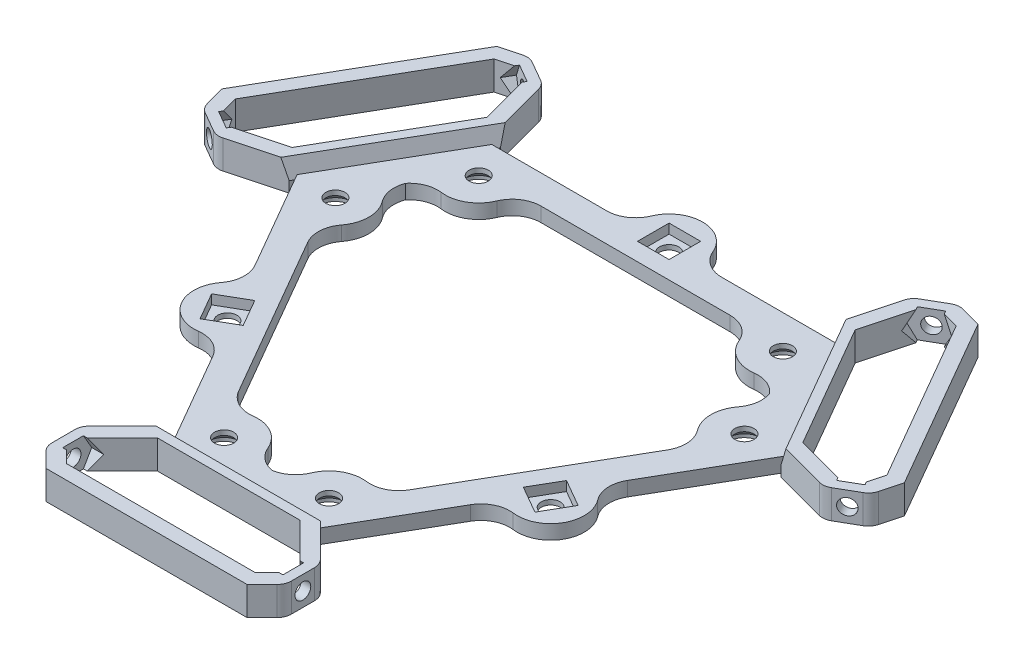
SolidWorks part; units mm, degrees
note: '?' marks a value the reader was unsure of.
ref_plane "Front Plane" through (0, 0, 0) normal (0, 0, 1) x (1, 0, 0)
ref_plane "Top Plane" through (0, 0, 0) normal (0, 1, 0) x (1, 0, 0)
ref_plane "Right Plane" through (0, 0, 0) normal (1, 0, 0) x (0, 0, -1)
sketch "Sketch1" plane through (0, 0, 0) normal (0, 1, 0) x (1, 0, 0)
  line L0 (-55.8013, 3.3494) -> (-30.8013, 46.6506) construction
  line L1 (50.8013, 12.0096) -> (35.8013, 37.9904)
  line L2 (35.8013, 37.9904) -> (-35.8013, 37.9904)
  line L3 (-35.8013, 37.9904) -> (-50.8013, 12.0096)
  line L4 (-50.8013, 12.0096) -> (-15, -50)
  line L5 (-15, -50) -> (15, -50)
  line L6 (15, -50) -> (50.8013, 12.0096)
  line L7 (55.8013, 3.3494) -> (30.8013, 46.6506) construction
  line L8 (-25, -50) -> (25, -50) construction
  line L9 (-43.8731, 12.0096) -> (-11.5359, -44) construction
  line L10 (-11.5359, -44) -> (11.5359, -44) construction
  line L11 (11.5359, -44) -> (43.8731, 12.0096) construction
  line L12 (43.8731, 12.0096) -> (32.3372, 31.9904) construction
  line L13 (32.3372, 31.9904) -> (-32.3372, 31.9904) construction
  line L14 (-32.3372, 31.9904) -> (-43.8731, 12.0096) construction
  line L15 (-43.8731, 12.0096) -> (-50.8013, 12.0096) construction
  line L16 (-32.3372, 31.9904) -> (-35.8013, 37.9904) construction
  line L17 (32.3372, 31.9904) -> (35.8013, 37.9904) construction
  line L18 (43.8731, 12.0096) -> (50.8013, 12.0096) construction
  line L19 (11.5359, -44) -> (15, -50) construction
  line L20 (-11.5359, -44) -> (-15, -50) construction
  line L21 (-40.1203, 18.5096) -> (-36.0899, 25.4904)
  line L22 (24.8316, 31.9904) -> (-24.8316, 31.9904)
  line L23 (-40.1203, 5.5096) -> (-15.2887, -37.5)
  line L24 (-4.0303, -44) -> (4.0303, -44)
  line L25 (40.1203, 5.5096) -> (15.2887, -37.5)
  line L26 (40.1203, 18.5096) -> (36.0899, 25.4904)
  circle A0 centre (0, 0) radius 37.9904 construction
  circle A1 centre (0, 0) radius 50 construction
  arc A2 (-40.1203, 5.5096) -> (-40.1203, 18.5096) centre (-42.7184, 12.0096) ccw
  arc A3 (-36.0899, 25.4904) -> (-24.8316, 31.9904) centre (-31.7598, 30.9904) ccw
  arc A4 (24.8316, 31.9904) -> (36.0899, 25.4904) centre (31.7598, 30.9904) ccw
  arc A5 (40.1203, 18.5096) -> (40.1203, 5.5096) centre (42.7184, 12.0096) ccw
  arc A6 (15.2887, -37.5) -> (4.0303, -44) centre (10.9585, -43) ccw
  arc A7 (-4.0303, -44) -> (-15.2887, -37.5) centre (-10.9585, -43) ccw
  circle A8 centre (-42.7184, 12.0096) radius 7 construction
  point P13 (-43.3013, 25)
  point P16 (43.3013, 25)
  point P19 (0, -50)
  point P53 (0, 0)
  dimension "D4" = 3
  dimension "D5" = 14
  dimension "D6" = 100
  dimension "D1" = 50
  dimension "D2" = 10
  dimension "D3" = 6
extrude "Boss-Extrude1" add sketch "Sketch1" along normal blind 3
sketch "Sketch2" plane through (0, 0, 0) normal (0, -1, 0) x (1, 0, 0)
  line L0 (25, 60.85) -> (25, 58.85)
  line L1 (25, 58.85) -> (16.15, 50)
  line L2 (16.15, 50) -> (-16.15, 50)
  line L3 (-15, 50) -> (15, 50) construction
  line L4 (0, 50) -> (0, 53) construction
  line L5 (-14.9074, 53) -> (14.9074, 53)
  line L6 (14.9074, 53) -> (22.7574, 60.85)
  line L7 (22.7574, 60.85) -> (25, 60.85) construction
  line L8 (18.8324, 56.925) -> (20.9537, 54.8037) construction
  line L9 (-4.8365, 62.5) -> (49995.1635, 62.5) construction
  line L10 (-18.8324, 56.925) -> (-20.9537, 54.8037) construction
  line L11 (-22.7574, 60.85) -> (-25, 60.85) construction
  line L12 (-14.9074, 53) -> (-22.7574, 60.85)
  line L13 (-25, 58.85) -> (-16.15, 50)
  line L14 (-25, 60.85) -> (-25, 58.85)
  line L15 (-25, 60.85) -> (-25, 64.15)
  line L16 (-22.7574, 64.15) -> (-25, 64.15) construction
  line L17 (-22.7574, 64.15) -> (-22.7574, 60.85)
  line L18 (22.7574, 60.85) -> (22.7574, 64.15)
  line L19 (-18.8324, 68.075) -> (-20.9537, 70.1963) construction
  line L20 (25, 64.15) -> (25, 60.85)
  line L21 (18.8324, 68.075) -> (20.9537, 70.1963) construction
  line L22 (22.7574, 64.15) -> (25, 64.15) construction
  line L23 (0, 70.15) -> (0, 67.15) construction
  line L24 (-25, 64.15) -> (-25, 66.15)
  line L25 (-25, 66.15) -> (-21, 70.15)
  line L26 (-19.7574, 67.15) -> (-22.7574, 64.15)
  line L27 (19.7574, 67.15) -> (22.7574, 64.15)
  line L28 (-19.7574, 67.15) -> (19.7574, 67.15)
  line L29 (21, 70.15) -> (-21, 70.15)
  line L30 (25, 66.15) -> (21, 70.15)
  line L31 (25, 64.15) -> (25, 66.15)
  point P23 (-25, 62.5)
  point P24 (-22.7574, 62.5)
  point P25 (22.7574, 62.5)
  point P35 (25, 62.5)
  dimension "D1" = 45
  dimension "D2" = 3
  dimension "D3" = 25
  dimension "D4" = 2
  dimension "D5" = 1.65
  dimension "D6" = 50
  dimension "D7" = 1
extrude "Boss-Extrude2" add sketch "Sketch2" against normal blind 6
sketch "Sketch3" plane through (25, 0, 0) normal (1, 0, 0) x (0, 0, -1)
  line L0 (-66.15, 6) -> (-58.85, 0) construction
  circle A0 centre (-62.5, 3) radius 1.65
  dimension "D1" = 3.3
extrude "Cut-Extrude1" cut sketch "Sketch3" against normal through all
sketch "Sketch4" plane through (-22.7574, 0, 0) normal (1, 0, 0) x (0, 0, -1)
  line L1 (-58.6029, 3) -> (-60.5514, 6.375)
  line L2 (-60.5514, 6.375) -> (-64.4486, 6.375)
  line L3 (-64.4486, 6.375) -> (-66.3971, 3)
  line L4 (-66.3971, 3) -> (-64.4486, -0.375)
  line L5 (-64.4486, -0.375) -> (-60.5514, -0.375)
  line L6 (-60.5514, -0.375) -> (-58.6029, 3)
  circle A0 centre (-62.5, 3) radius 3.375 construction
  dimension "D1" = 6.75
extrude "Cut-Extrude2" cut sketch "Sketch4" against normal offset from surface 2 and the other way offset from surface (45.7574 mm away) 2 up to face at (-25, 3, 64.15) other way up to face at (25, 3, 60.85)
ref_axis "Axis1" through (0, 6.3, 0) along (0, -1, 0)?
pattern_circular "CirPattern2" count 3 over 360 about axis through (0, 0, 0) along (0, 1, 0) of "Boss-Extrude2", "Cut-Extrude1"
sketch "Sketch6" plane through (-11.3787, 0, -19.7085) normal (0.5, 0, 0.866) x (0.866, 0, -0.5)
  line L1 (58.6029, 3) -> (60.5514, -0.375)
  line L2 (60.5514, -0.375) -> (64.4486, -0.375)
  line L3 (64.4486, -0.375) -> (66.3971, 3)
  line L4 (66.3971, 3) -> (64.4486, 6.375)
  line L5 (64.4486, 6.375) -> (60.5514, 6.375)
  line L6 (60.5514, 6.375) -> (58.6029, 3)
  circle A0 centre (62.5, 3) radius 3.375 construction
  dimension "D1" = 6.75
extrude "Cut-Extrude4" cut sketch "Sketch6" against normal offset from surface 2 and the other way offset from surface (45.7574 mm away) 2 up to face at (40.1976, 3, -52.0756)
sketch "Sketch7" plane through (-11.3787, 0, 19.7085) normal (0.5, 0, -0.866) x (-0.866, 0, -0.5)
  line L1 (58.6029, 3) -> (60.5514, -0.375)
  line L2 (60.5514, -0.375) -> (64.4486, -0.375)
  line L3 (64.4486, -0.375) -> (66.3971, 3)
  line L4 (66.3971, 3) -> (64.4486, 6.375)
  line L5 (64.4486, 6.375) -> (60.5514, 6.375)
  line L6 (60.5514, 6.375) -> (58.6029, 3)
  circle A0 centre (62.5, 3) radius 3.375 construction
  dimension "D1" = 6.75
extrude "Cut-Extrude5" cut sketch "Sketch7" against normal offset from surface 2 and the other way offset from surface (45.7574 mm away) 2 up to face at (-65.1976, 3, -8.7744)
sketch "Sketch5" plane through (0, 3, 0) normal (0, 1, 0) x (1, 0, 0)
  circle A0 centre (42.7184, 12.0096) radius 2
  circle A1 centre (31.7598, 30.9904) radius 2
  circle A2 centre (10.9585, -43) radius 2
  circle A3 centre (-10.9585, -43) radius 2
  circle A4 centre (-42.7184, 12.0096) radius 2
  circle A5 centre (-31.7598, 30.9904) radius 2
  point P6 (0, 0)
  point P19 (0, 0)
  dimension "D1" = 4
  dimension "D2" = 3
extrude "Cut-Extrude3" cut sketch "Sketch5" against normal through all
chamfer "Chamfer1" distance 1 angle 75 3 edges at (43.3013, 6, -25) (0, 6, 50) (-43.3013, 6, -25)
fillet "Fillet2" radius 3 12 edges at (63.4656, 3, -7.7744) (69.7876, 3, -11.4244) (44.7876, 3, -54.7256) (38.4656, 3, -51.0756) (-44.7876, 3, -54.7256) (-38.4656, 3, -51.0756) (-63.4656, 3, -7.7744) (-69.7876, 3, -11.4244) (-25, 3, 66.15) (-25, 3, 58.85) (25, 3, 66.15) (25, 3, 58.85)
sketch "Sketch8" plane through (0, 0, 0) normal (0, -1, 0) x (1, 0, 0)
  circle A0 centre (31.7598, -30.9904) radius 3.3
  circle A1 centre (42.7184, -12.0096) radius 3.3
  circle A2 centre (10.9585, 43) radius 3.3
  circle A3 centre (-10.9585, 43) radius 3.3
  circle A4 centre (-42.7184, -12.0096) radius 3.3
  circle A5 centre (-31.7598, -30.9904) radius 3.3
  dimension "D1" = 6.6
extrude "Cut-Extrude6" cut sketch "Sketch8" against normal blind 2
chamfer "Chamfer2" distance 1.3 angle 45 6 edges at (31.7598, 2, -34.2904) (42.7184, 2, -15.3096) (10.9585, 2, 39.7) (-10.9585, 2, 39.7) (-42.7184, 2, -15.3096) (-31.7598, 2, -34.2904)
sketch "Sketch9" plane through (0, 0, 0) normal (0, -1, 0) x (1, 0, 0)
  line L0 (-32.9006, 18.9952) -> (-33.7667, 19.4952) construction
  line L1 (-50.8013, -12.0096) -> (-15, 50) construction
  line L2 (-40.1203, -5.5096) -> (-15.2887, 37.5) construction
  line L3 (32.9006, 18.9952) -> (33.7667, 19.4952) construction
  line L4 (0, -37.9904) -> (0, -38.9904) construction
  circle A0 centre (-33.7667, 19.4952) radius 7
  circle A1 centre (33.7667, 19.4952) radius 7
  circle A2 centre (0, -38.9904) radius 7
  point P19 (0, 0)
  dimension "D1" = 14
  dimension "D2" = 3
extrude "Boss-Extrude3" add sketch "Sketch9" against normal up to surface (3 mm away) up to face at (-42.7184, 3, -10.0096)
sketch "Sketch10" plane through (0, 3, 0) normal (0, 1, 0) x (1, 0, 0)
  line L0 (32.5588, -14.9873) -> (29.2588, -20.7031)
  line L1 (-3.3, 35.6904) -> (3.3, 35.6904)
  line L2 (-3.3, 35.6904) -> (-3.3, 42.2904)
  line L3 (-3.3, 42.2904) -> (3.3, 42.2904)
  line L4 (3.3, 35.6904) -> (3.3, 42.2904)
  line L5 (-3.3, 35.6904) -> (3.3, 42.2904) construction
  line L6 (-3.3, 42.2904) -> (3.3, 35.6904) construction
  line L7 (32.5588, -14.9873) -> (38.2745, -18.2873)
  line L8 (38.2745, -18.2873) -> (34.9745, -24.0031)
  line L9 (29.2588, -20.7031) -> (34.9745, -24.0031)
  line L10 (32.5588, -14.9873) -> (34.9745, -24.0031) construction
  line L11 (38.2745, -18.2873) -> (29.2588, -20.7031) construction
  line L12 (-29.2588, -20.7031) -> (-32.5588, -14.9873)
  line L13 (-29.2588, -20.7031) -> (-34.9745, -24.0031)
  line L14 (-34.9745, -24.0031) -> (-38.2745, -18.2873)
  line L15 (-32.5588, -14.9873) -> (-38.2745, -18.2873)
  line L16 (-29.2588, -20.7031) -> (-38.2745, -18.2873) construction
  line L17 (-34.9745, -24.0031) -> (-32.5588, -14.9873) construction
  point P0 (0, 38.9904)
  point P8 (33.7667, -19.4952)
  point P13 (-33.7667, -19.4952)
  point P18 (0, 0)
  dimension "D1" = 6.6
  dimension "D2" = 3
extrude "Cut-Extrude7" cut sketch "Sketch10" against normal blind 2
sketch "Sketch11" plane through (0, 3, 0) normal (0, 1, 0) x (1, 0, 0)
  circle A0 centre (-33.7667, -19.4952) radius 2
  circle A1 centre (33.7667, -19.4952) radius 2
  circle A2 centre (0, 38.9904) radius 2
  dimension "D1" = 4
extrude "Cut-Extrude8" cut sketch "Sketch11" against normal through all
fillet "Fillet1" radius 6 18 edges at (-40.1203, 1.5, -18.5096) (-15.2887, 1.5, 37.5) (-4.0303, 1.5, 44) (4.0303, 1.5, 44) (15.2887, 1.5, 37.5) (40.1203, 1.5, -5.5096) (40.1203, 1.5, -18.5096) (36.0899, 1.5, -25.4904) (24.8316, 1.5, -31.9904) (-24.8316, 1.5, -31.9904) (-36.0899, 1.5, -25.4904) (-40.1203, 1.5, -5.5096) (-29.4365, 1.5, 24.9952) (-36.3647, 1.5, 12.9952) (36.3647, 1.5, 12.9952) (29.4365, 1.5, 24.9952) (-6.9282, 1.5, -37.9904) (6.9282, 1.5, -37.9904)
